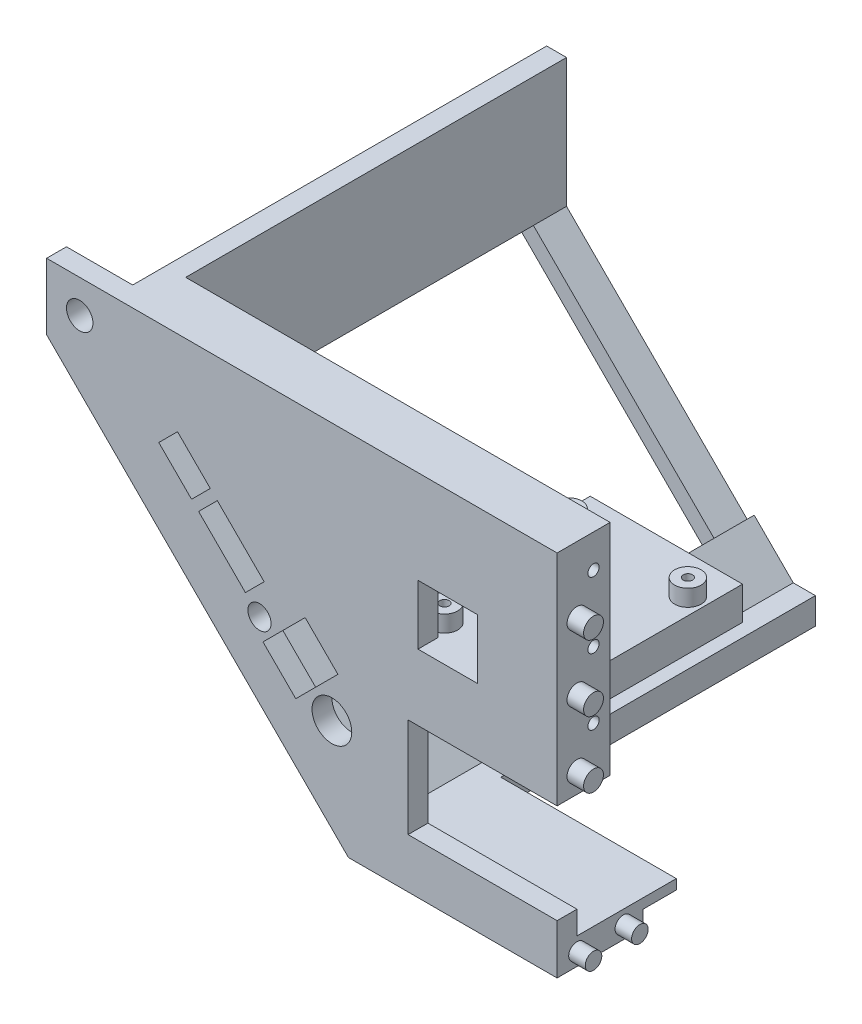
SolidWorks part; units mm, degrees
ref_plane "Plan de face" through (0, 0, 0) normal (0, 0, 1) x (1, 0, 0)
ref_plane "Plan de dessus" through (0, 0, 0) normal (0, 1, 0) x (1, 0, 0)
ref_plane "Plan de droite" through (0, 0, 0) normal (1, 0, 0) x (0, 0, -1)
sketch "Esquisse1" plane through (0, 0, 0) normal (0, 0, 1) x (1, 0, 0)
  line L0 (-63, 0) -> (0, 0)
  line L1 (0, 0) -> (0, 111.15)
  line L2 (-154.15, 91.15) -> (-154.15, 111.15)
  line L3 (-154.15, 91.15) -> (-63, 0)
  line L4 (-154.15, 111.15) -> (0, 111.15)
  dimension "D1" = 135
  dimension "D2" = 20
  dimension "D3" = 63
  dimension "D4" = 154.15
extrude "Boss.-Extru.1" add sketch "Esquisse1" along normal blind 6
sketch "Esquisse3" plane through (0, 0, 0) normal (0, 0, -1) x (-1, 0, 0)
  line L0 (0, 0) -> (0, 8)
  line L1 (0, 0) -> (0, 111.15) construction
  line L2 (0, 8) -> (59.6863, 8)
  line L3 (59.6863, 8) -> (142.8363, 91.15)
  line L4 (142.8363, 91.15) -> (154.15, 91.15)
  line L5 (154.15, 91.15) -> (63, 0)
  line L6 (154.15, 91.15) -> (63, 0) construction
  line L7 (63, 0) -> (0, 0) construction
  line L8 (63, 0) -> (0, 0)
  dimension "D1" = 8
  dimension "D2" = 8
extrude "Boss.-Extru.2" add sketch "Esquisse3" along normal blind 30
sketch "Esquisse4" plane through (0, 0, 0) normal (0, -1, 0) x (-1, 0, 0)
  line L0 (63, -6) -> (63, 30) construction
  line L1 (0, 20) -> (53, 20)
  line L2 (0, 20) -> (0, 30)
  line L3 (0, 30) -> (53, 30)
  line L4 (53, 20) -> (53, 30)
  point P4 (0, 0)
  dimension "D1" = 10
  dimension "D2" = 10
extrude "Enlèv. mat.-Extru.1" cut sketch "Esquisse4" against normal blind 5
sketch "Esquisse5" plane through (-31.5, -31.5, 0) normal (-0.7071, -0.7071, 0) x (0, 0, 1)
  line L0 (-30, 44.5477) -> (-30, 173.4533) construction
  line L1 (-20, 151.5477) -> (-30, 151.5477)
  line L2 (-20, 151.5477) -> (-20, 64.5477)
  line L3 (-20, 64.5477) -> (-30, 64.5477)
  line L4 (-30, 151.5477) -> (-30, 64.5477)
  line L6 (6, 44.5477) -> (-30, 44.5477) construction
  dimension "D1" = 87
  dimension "D2" = 20
  dimension "D3" = 10
extrude "Enlèv. mat.-Extru.2" cut sketch "Esquisse5" against normal blind 5
sketch "Esquisse6" plane through (0, 0, 6) normal (0, 0, 1) x (1, 0, 0)
  line L0 (0, 0) -> (0, 111.15) construction
  line L1 (0, 45) -> (-45, 45)
  line L2 (0, 45) -> (0, 15)
  line L3 (0, 15) -> (-45, 15)
  line L4 (-45, 45) -> (-45, 15)
  dimension "D1" = 45
  dimension "D2" = 45
  dimension "D3" = 30
extrude "Enlèv. mat.-Extru.3" cut sketch "Esquisse6" against normal through all
sketch "Esquisse7" plane through (0, 0, 6) normal (0, 0, 1) x (1, 0, 0)
  line L0 (-114.6188, 85.5599) -> (-120.2756, 79.9031)
  line L1 (-120.2756, 79.9031) -> (-110.3762, 70.0036)
  line L2 (-110.3762, 70.0036) -> (-104.7193, 75.6604)
  line L3 (-104.7193, 75.6604) -> (-114.6188, 85.5599)
  line L4 (-108.2548, 67.8823) -> (-94.1127, 53.7401)
  line L5 (-94.1127, 53.7401) -> (-88.4558, 59.397)
  line L6 (-88.4558, 59.397) -> (-102.598, 73.5391)
  line L7 (-102.598, 73.5391) -> (-108.2548, 67.8823)
  line L8 (-76.0815, 56.215) -> (-88.8094, 43.4871)
  line L9 (-88.8094, 43.4871) -> (-78.9099, 33.5876)
  line L10 (-78.9099, 33.5876) -> (-66.182, 46.3155)
  line L11 (-154.15, 91.15) -> (-63, 0) construction
  line L12 (-76.0815, 56.215) -> (-66.182, 46.3155)
  circle A0 centre (-89.8701, 49.4975) radius 3.5
  circle A2 centre (-68, 33.2843) radius 6
  point P19 (-87.7487, 24.7487)
  point P21 (-105.4264, 42.4264)
  point P25 (-121.6899, 58.6899)
  dimension "D2" = 7
  dimension "D8" = 12
  dimension "D15" = 5
  dimension "D1" = 16
  dimension "D3" = 16
  dimension "D4" = 20
  dimension "D5" = 8
  dimension "D6" = 14
  dimension "D7" = 5
  dimension "D9" = 18
  dimension "D10" = 35
  dimension "D11" = 14
  dimension "D12" = 20
  dimension "D13" = 83
  dimension "D14" = 60
extrude "Enlèv. mat.-Extru.4" cut sketch "Esquisse7" against normal up to surface (6 mm away) up to face at (-60.0823, 54.06, 0)
sketch "Esquisse11" plane through (0, 0, 0) normal (0, 0, -1) x (-1, 0, 0)
  line L1 (10, 105.15) -> (128.15, 105.15)
  line L2 (0, 111.15) -> (0, 45)
  line L3 (45, 55) -> (45, 45)
  line L4 (10, 105.15) -> (10, 55)
  line L5 (128.15, 105.15) -> (128.15, 76.4637)
  line L6 (0, 111.15) -> (154.15, 111.15) construction
  line L7 (134.15, 111.15) -> (0, 111.15)
  line L8 (134.15, 91.15) -> (142.8363, 91.15)
  line L9 (134.15, 91.15) -> (134.15, 111.15)
  line L10 (0, 45) -> (45, 45) construction
  line L11 (10, 55) -> (45, 55)
  line L12 (142.8363, 91.15) -> (128.15, 76.4637)
  line L13 (154.15, 91.15) -> (142.8363, 91.15) construction
  line L14 (142.8363, 91.15) -> (59.6863, 8) construction
  line L15 (0, 45) -> (45, 45)
  line L16 (45, 45) -> (45, 15) construction
  dimension "D1" = 10
  dimension "D2" = 20
  dimension "D3" = 6
  dimension "D4" = 6
  dimension "D5" = 10
extrude "Boss.-Extru.4" add sketch "Esquisse11" along normal blind 10
hole_wizard "Fraisage pour vis à tête fraisée M31" positions "Esquisse9" profile "Esquisse10" countersink size "M3" standard "Ansi Metric" end condition through all
sketch "Esquisse9" plane through (-10, 0, 0) normal (-1, 0, 0) x (0, 0, 1)
  line L1 (-10, 55) -> (-10, 105.15) construction
  line L2 (6, 111.15) -> (-10, 111.15) construction
  point P0 (-5, 101.15)
  dimension "D1" = 10
  dimension "D2" = 5
sketch "Esquisse10" plane through (-10, 101.15, -5) normal (0, 1, 0) x (0, 0, 1)
  line L0 (0, 0) -> (0, 10)
  line L1 (0, 10) -> (1.7, 10)
  line L2 (1.7, 10) -> (1.7, 1.45)
  line L3 (1.7, 1.45) -> (3.15, 0)
  line L5 (3.15, 0) -> (0, 0)
  line L6 (-1.7, 1.45) -> (-3.15, 0) construction
  line L11 (0, -6.35) -> (0, 107.95) construction
  dimension "Diamètre du perçage jusqu'au prochain" = 3.4
  dimension "Profondeur du perçage jusqu'au prochain" = 10
  dimension "Diamètre du fraisage entrant" = 6.3
  dimension "Angle du fraisage entrant" = 90
pattern_linear "Répétition linéaire1" count 3 spacing 20 along (0, -1, 0) of "Fraisage pour vis à tête fraisée M31"
sketch "Esquisse12" plane through (0, 0, 0) normal (1, 0, 0) x (0, 0, -1)
  line L0 (-6, 45) -> (-6, 111.15) construction
  line L1 (-6, 0) -> (20, 0) construction
  line L2 (-6, 111.15) -> (10, 111.15) construction
  line L3 (-6, 0) -> (-6, 15) construction
  circle A0 centre (0, 71.15) radius 3
  circle A1 centre (0, 91.15) radius 3
  circle A2 centre (0, 4) radius 2.5
  circle A3 centre (0, 51.15) radius 3
  circle A4 centre (14, 4) radius 2.5
  point P18 (0, 0)
  dimension "D1" = 5
  dimension "D2" = 6
  dimension "D3" = 6
  dimension "D4" = 20
  dimension "D5" = 20
  dimension "D6" = 20
  dimension "D7" = 4
  dimension "D8" = 20
extrude "Boss.-Extru.5" add sketch "Esquisse12" along normal blind 5
sketch "Esquisse13" plane through (0, 0, 6) normal (0, 0, 1) x (1, 0, 0)
  line L0 (-154.15, 111.15) -> (-154.15, 91.15) construction
  circle A0 centre (-144.15, 101.15) radius 4
  point P4 (-154.15, 101.15)
  dimension "D2" = 8
  dimension "D1" = 10
extrude "Enlèv. mat.-Extru.5" cut sketch "Esquisse13" against normal through all
sketch "Esquisse14" plane through (0, 0, 0) normal (0, 0, -1) x (-1, 0, 0)
  line L0 (0, 111.15) -> (0, 45) construction
  line L1 (10, 65) -> (56, 65)
  line L2 (10, 65) -> (10, 55)
  line L3 (10, 55) -> (56, 55)
  line L4 (56, 65) -> (56, 55)
  line L5 (0, 0) -> (53, 0) construction
  dimension "D1" = 10
  dimension "D2" = 46
  dimension "D3" = 10
  dimension "D4" = 55
extrude "Boss.-Extru.6" add sketch "Esquisse14" along normal blind 60
sketch "Esquisse15" plane through (0, 0, 0) normal (0, 0, -1) x (-1, 0, 0)
  line L0 (56, 65) -> (10, 65) construction
  line L1 (24, 65) -> (42, 65)
  line L2 (24, 65) -> (24, 83)
  line L3 (24, 83) -> (42, 83)
  line L4 (42, 65) -> (42, 83)
  point P4 (33, 65)
  point P5 (33, 65)
  point P8 (0, 0)
  point P9 (34.8441, 65)
  point P10 (33, 65)
  dimension "D1" = 18
  dimension "D2" = 18
extrude "Enlèv. mat.-Extru.6" cut sketch "Esquisse15" against normal up to next
sketch "Esquisse16" plane through (0, 65, 0) normal (0, 1, 0) x (1, 0, 0)
  line L0 (-10, 60) -> (-10, 10) construction
  line L1 (-56, 60) -> (-56, 0) construction
  line L3 (-24, 0) -> (-10, 0) construction
  circle A0 centre (-21, 5) radius 4
  circle A1 centre (-15, 48.5) radius 4
  circle A2 centre (-51, 48.5) radius 4
  circle A3 centre (-45, 5) radius 4
  point P8 (0, 0)
  point P15 (0, 0)
  point P16 (0, 0)
  dimension "D1" = 8
  dimension "D2" = 5
  dimension "D3" = 5
  dimension "D4" = 48.5
  dimension "D5" = 11
  dimension "D6" = 11
  dimension "D7" = 5
extrude "Boss.-Extru.7" add sketch "Esquisse16" along normal blind 5
sketch "Esquisse17" plane through (0, 70, 0) normal (0, 1, 0) x (1, 0, 0)
  circle A0 centre (-21, 5) radius 1.4
  circle A1 centre (-21, 5) radius 4 construction
  circle A2 centre (-45, 5) radius 1.4
  circle A3 centre (-15, 48.5) radius 1.4
  circle A4 centre (-51, 48.5) radius 1.4
  dimension "D1" = 2.8
extrude "Enlèv. mat.-Extru.7" cut sketch "Esquisse17" against normal up to surface (15 mm away) up to face at (-37, 55, -23.3333)
sketch "Esquisse18" plane through (0, 0, -10) normal (0, 0, -1) x (-1, 0, 0)
  line L0 (128.15, 111.15) -> (128.15, 72.2211)
  line L1 (128.15, 105.15) -> (128.15, 76.4637) construction
  line L3 (128.15, 72.2211) -> (135.1249, 79.196)
  line L4 (135.1249, 79.196) -> (138.6604, 75.6604)
  line L5 (138.6604, 75.6604) -> (154.15, 91.15)
  line L6 (154.15, 91.15) -> (134.15, 91.15)
  line L8 (134.15, 91.15) -> (134.15, 111.15)
  line L9 (134.15, 111.15) -> (128.15, 111.15)
  line L10 (134.15, 111.15) -> (0, 111.15) construction
  line L11 (71.4853, 19.799) -> (59.6863, 8)
  line L12 (59.6863, 8) -> (53, 8)
  line L13 (53, 8) -> (53, 0)
  line L14 (53, 0) -> (63, 0)
  line L15 (63, 0) -> (77.1421, 14.1421)
  line L16 (77.1421, 14.1421) -> (71.4853, 19.799)
  line L17 (142.8363, 91.15) -> (59.6863, 8) construction
  line L18 (63, 0) -> (77.1421, 14.1421) construction
  line L19 (73.6066, 17.6777) -> (77.1421, 14.1421) construction
  line L20 (59.6863, 8) -> (0, 8) construction
  line L21 (53, 5) -> (53, 0) construction
  line L22 (135.1249, 79.196) -> (73.6066, 17.6777) construction
  point P2 (0, 0)
  point P3 (128.306, 76.6197)
  point P15 (0, 0)
  point P16 (124.7578, 73.0715)
  point P29 (75.4345, 12.4345)
  point P33 (0, 0)
  point P35 (0, 0)
  point P41 (0, 0)
  point P42 (0, 0)
extrude "Boss.-Extru.8" add sketch "Esquisse18" along normal blind 115
sketch "Esquisse20" plane through (-27.9645, -27.9645, 0) normal (-0.7071, -0.7071, 0) x (0, 0, 1)
  line L0 (-125, 64.5477) -> (-20, 64.5477) construction
  line L1 (-115, 64.5477) -> (-125, 64.5477)
  line L2 (-115, 64.5477) -> (-115, 151.5477)
  line L3 (-115, 151.5477) -> (-125, 151.5477)
  line L4 (-125, 64.5477) -> (-125, 151.5477)
  line L5 (-20, 151.5477) -> (-125, 151.5477) construction
  line L6 (-125, 141.6837) -> (-125, 151.5477) construction
  point P8 (-94.0875, 64.5477)
  point P9 (-125, 151.5477)
  dimension "D1" = 10
extrude "Boss.-Extru.9" add sketch "Esquisse20" along normal up to surface (5 mm away) up to face at (-113.3395, 50.3395, -58.6667)
